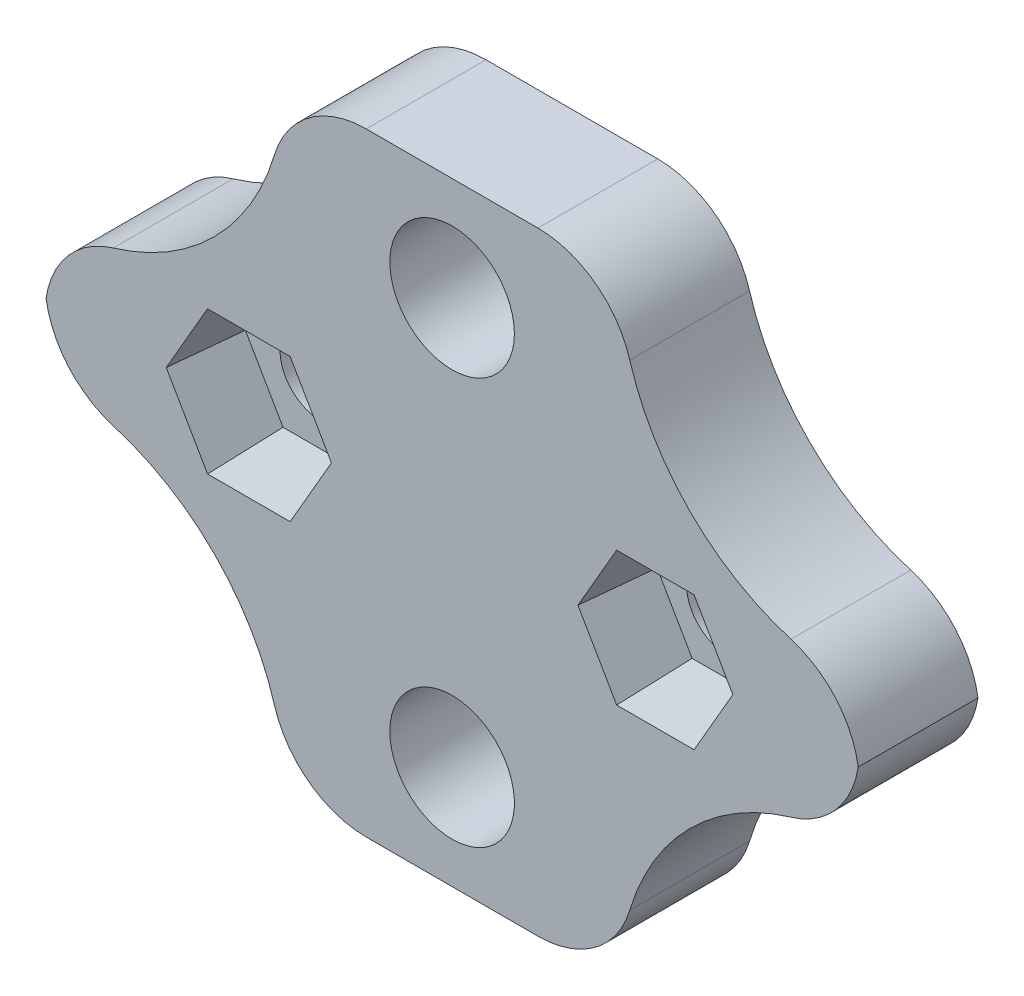
SolidWorks part; units mm, degrees
ref_plane "Plan de face" through (0, 0, 0) normal (0, 0, 1) x (1, 0, 0)
ref_plane "Plan de dessus" through (0, 0, 0) normal (0, 1, 0) x (1, 0, 0)
ref_plane "Plan de droite" through (0, 0, 0) normal (1, 0, 0) x (0, 0, -1)
sketch "Esquisse1" plane through (0, 0, 0) normal (0, 0, 1) x (1, 0, 0)
  line L0 (-11.7267, 0) -> (-3.2414, 8.4853) construction
  line L1 (-11.7267, 0) -> (3.8892, 0) construction
  line L2 (-3.2414, 8.4853) -> (-3.2414, -3.4304) construction
  line L3 (-3.2414, 12.8) -> (-3.2414, -12.8) construction
  line L4 (-20.2414, -12.8) -> (13.7586, -12.8)
  line L5 (-20.2414, -12.8) -> (-20.2414, 12.8)
  line L6 (-20.2414, 12.8) -> (13.7586, 12.8)
  line L7 (13.7586, -12.8) -> (13.7586, 12.8)
  line L8 (-20.2414, -12.8) -> (13.7586, 12.8) construction
  line L9 (-20.2414, 12.8) -> (13.7586, -12.8) construction
  line L10 (13.7586, 0) -> (-20.2414, 0) construction
  circle A0 centre (-11.7267, 0) radius 1.7
  circle A1 centre (-3.2414, 8.4853) radius 2.6
  circle A2 centre (-3.2414, -8.4853) radius 2.6
  circle A3 centre (5.2438, 0) radius 1.7
  point P12 (-3.2414, 0)
  dimension "D1" = 34
  dimension "D2" = 25.6
extrude "Boss.-Extru.1" add sketch "Esquisse1" along normal blind 5
sketch "Esquisse3" plane through (0, 0, 5) normal (0, 0, 1) x (1, 0, 0)
  line L1 (-8.2785, 0) -> (-10.0026, 2.9863)
  line L2 (-10.0026, 2.9863) -> (-13.4509, 2.9863)
  line L3 (-13.4509, 2.9863) -> (-15.175, 0)
  line L4 (-15.175, 0) -> (-13.4509, -2.9863)
  line L5 (-13.4509, -2.9863) -> (-10.0026, -2.9863)
  line L6 (-10.0026, -2.9863) -> (-8.2785, 0)
  line L7 (8.477, 0) -> (6.8604, 2.8)
  line L8 (6.8604, 2.8) -> (3.6273, 2.8)
  line L9 (3.6273, 2.8) -> (2.0107, 0)
  line L10 (2.0107, 0) -> (3.6273, -2.8)
  line L11 (3.6273, -2.8) -> (6.8604, -2.8)
  line L12 (6.8604, -2.8) -> (8.477, 0)
  circle A0 centre (-11.7267, 0) radius 2.9863 construction
  circle A1 centre (5.2438, 0) radius 2.8 construction
extrude "Enlèv. mat.-Extru.2" cut sketch "Esquisse3" against normal blind 3 draft 5
sketch "Esquisse4" plane through (0, 0, 0) normal (0, 0, -1) x (-1, 0, 0)
  line L0 (-13.7586, 12.8) -> (20.2414, 12.8) construction
  line L1 (20.2414, 12.8) -> (20.2414, -12.8) construction
  line L2 (10.2414, 12.8) -> (20.2414, 12.8)
  line L3 (20.2414, 12.8) -> (20.2414, 2.8)
  line L4 (20.2414, 0) -> (16.9092, 0) construction
  line L5 (20.2414, -12.8) -> (20.2414, -2.8)
  line L6 (10.2414, -12.8) -> (20.2414, -12.8)
  line L7 (3.2414, 12.8) -> (3.2414, 4.8202) construction
  line L8 (-3.7586, -12.8) -> (-13.7586, -12.8)
  line L9 (-13.7586, -12.8) -> (-13.7586, -2.8)
  line L10 (-13.7586, 12.8) -> (-13.7586, 2.8)
  line L11 (-3.7586, 12.8) -> (-13.7586, 12.8)
  arc A0 (10.2414, 12.8) -> (20.2414, 2.8) centre (20.2414, 12.8) ccw
  arc A1 (10.2414, -12.8) -> (20.2414, -2.8) centre (20.2414, -12.8) cw
  arc A2 (-3.7586, -12.8) -> (-13.7586, -2.8) centre (-13.7586, -12.8) ccw
  arc A3 (-3.7586, 12.8) -> (-13.7586, 2.8) centre (-13.7586, 12.8) cw
extrude "Enlèv. mat.-Extru.3" cut sketch "Esquisse4" against normal blind 10
fillet "Congé1" radius 4 8 edges at (-10.2414, -12.8, 2.5) (-20.2414, -2.8, 2.5) (-20.2414, 2.8, 2.5) (-10.2414, 12.8, 2.5) (3.7586, -12.8, 2.5) (13.7586, -2.8, 2.5) (13.7586, 2.8, 2.5) (3.7586, 12.8, 2.5)
